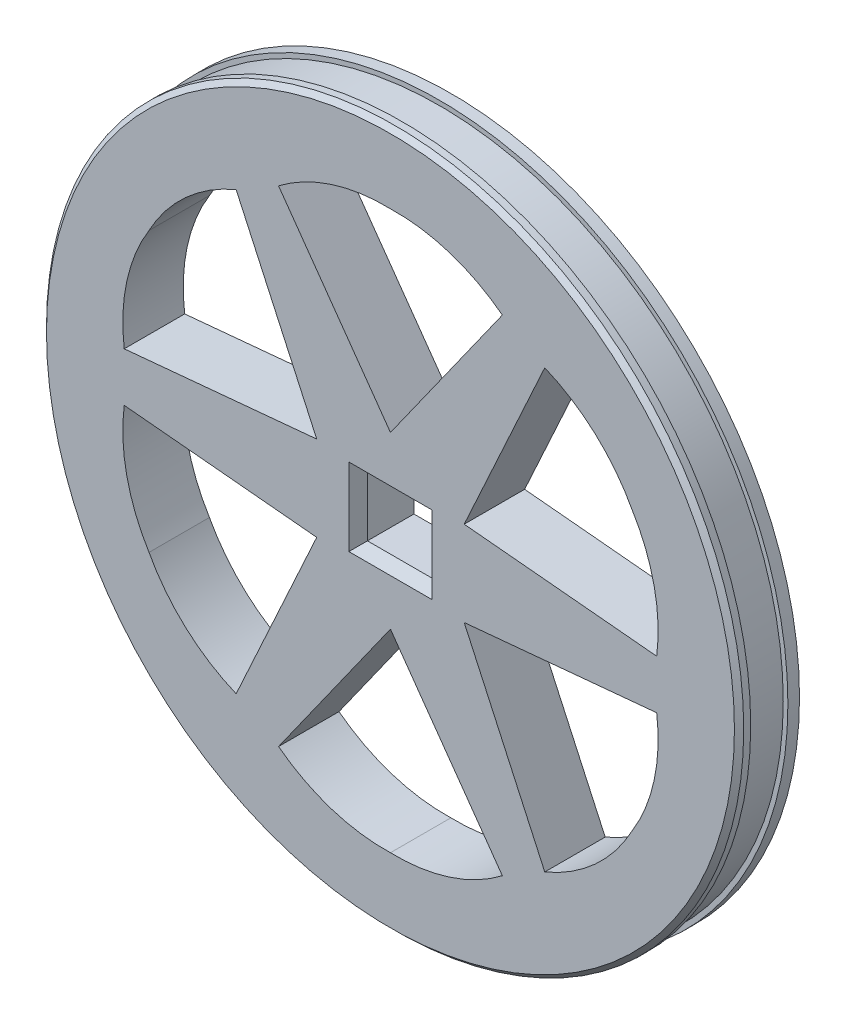
SolidWorks part; units mm, degrees
ref_plane "Front Plane" through (0, 0, 0) normal (0, 0, 1) x (1, 0, 0)
ref_plane "Top Plane" through (0, 0, 0) normal (0, 1, 0) x (1, 0, 0)
ref_plane "Right Plane" through (0, 0, 0) normal (1, 0, 0) x (0, 0, -1)
sketch "Sketch1" plane through (0, 0, 0) normal (0, 0, 1) x (1, 0, 0)
  line L1 (3.975, -3.675) -> (-3.975, -3.675)
  line L2 (3.975, -3.675) -> (3.975, 3.675)
  line L3 (3.975, 3.675) -> (-3.975, 3.675)
  line L4 (-3.975, -3.675) -> (-3.975, 3.675)
  circle A0 centre (0, 0) radius 37.5
  point P3 (0, 3.675)
  point P9 (3.975, 0)
  dimension "D1" = 75
  dimension "D2" = 7.95
  dimension "D3" = 7.35
extrude "Boss-Extrude1" add sketch "Sketch1" along normal mid plane 6.5
sketch "Sketch2" plane through (0, 0, 0) normal (0, 0, 1) x (1, 0, 0)
  line L0 (0, 0) -> (0, 32.5712) construction
  line L1 (0, 9.1586) -> (-12.0371, 26.1152)
  line L2 (0, 9.1586) -> (12.0371, 26.1152)
  arc A0 (-12.0371, 26.1152) -> (0, 29.9881) centre (-0.5568, 11.0765) cw
  arc A1 (12.0371, 26.1152) -> (0, 29.9881) centre (0.5568, 11.0765) ccw
extrude "Cut-Extrude1" cut sketch "Sketch2" along normal mid plane 8
pattern_circular "CirPattern1" count 6 over 360 about axis through (0, 0, 3.25) along (0, 0, -1) of "Cut-Extrude1" reverse direction yes
sketch "Sketch3" plane through (0, 0, 0) normal (0, 0, 1) x (1, 0, 0)
  circle A0 centre (0, 0) radius 37.5
  circle A1 centre (0, 0) radius 37
  circle A2 centre (0, 0) radius 37.5 construction
  dimension "D1" = 0.5
extrude "Cut-Extrude2" cut sketch "Sketch3" against normal mid plane 4
chamfer "Chamfer1" distance 0.5 distance2 1.5 4 edges at (3.975, 0, 3.25) (0, 3.675, 3.25) (-3.975, 0, 3.25) (0, -3.675, 3.25) first distance on face at (37.5, 0, 3.25)
chamfer "Chamfer2" distance 0.5 angle 45 1 edges at (37.5, 0, 3.25)
